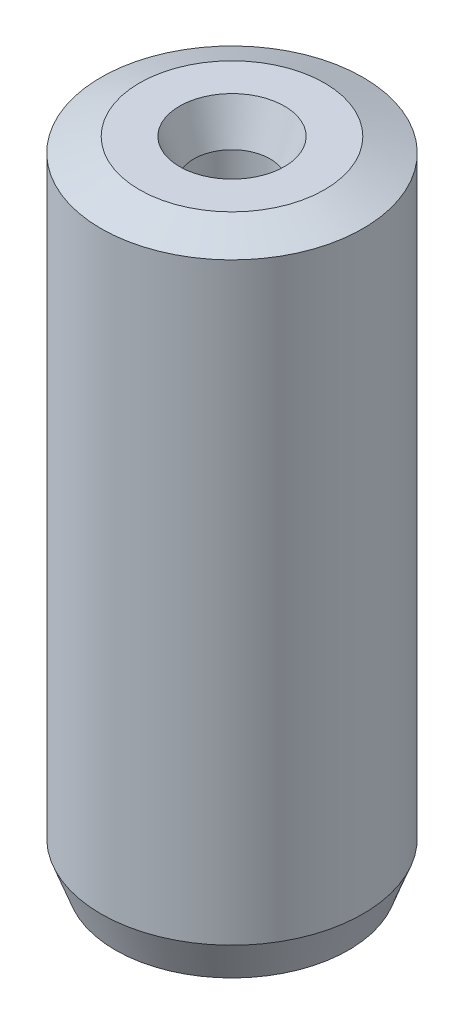
SolidWorks part; units mm, degrees
ref_plane "Front Plane" through (0, 0, 0) normal (0, 0, 1) x (1, 0, 0)
ref_plane "Top Plane" through (0, 0, 0) normal (0, 1, 0) x (1, 0, 0)
ref_plane "Right Plane" through (0, 0, 0) normal (1, 0, 0) x (0, 0, -1)
sketch "Sketch1" plane through (0, 0, 0) normal (0, 1, 0) x (1, 0, 0)
  circle A0 centre (0, 0) radius 5
  dimension "SLEEVE_OD" = 10
extrude "Boss-Extrude1" add sketch "Sketch1" along normal blind 24.6692
sketch "Sketch2" plane through (0, 0, 0) normal (0, 1, 0) x (1, 0, 0)
  circle A0 centre (0, 0) radius 1.4533
  dimension "BORE_D" = 2.9066
extrude "Cut-Extrude1" cut sketch "Sketch2" along normal through all
chamfer "Chamfer1" distance 0.5481 angle 69.539 4 edges at (0, 24.6692, 1.4533) (0, 0, 1.4533) (0, 0, 5) (0, 24.6692, 5) first distance on face at (0, 24.6692, 1.4533) first distance on face at (0, 0, 1.4533) first distance on face at (0, 24.6692, 5)
